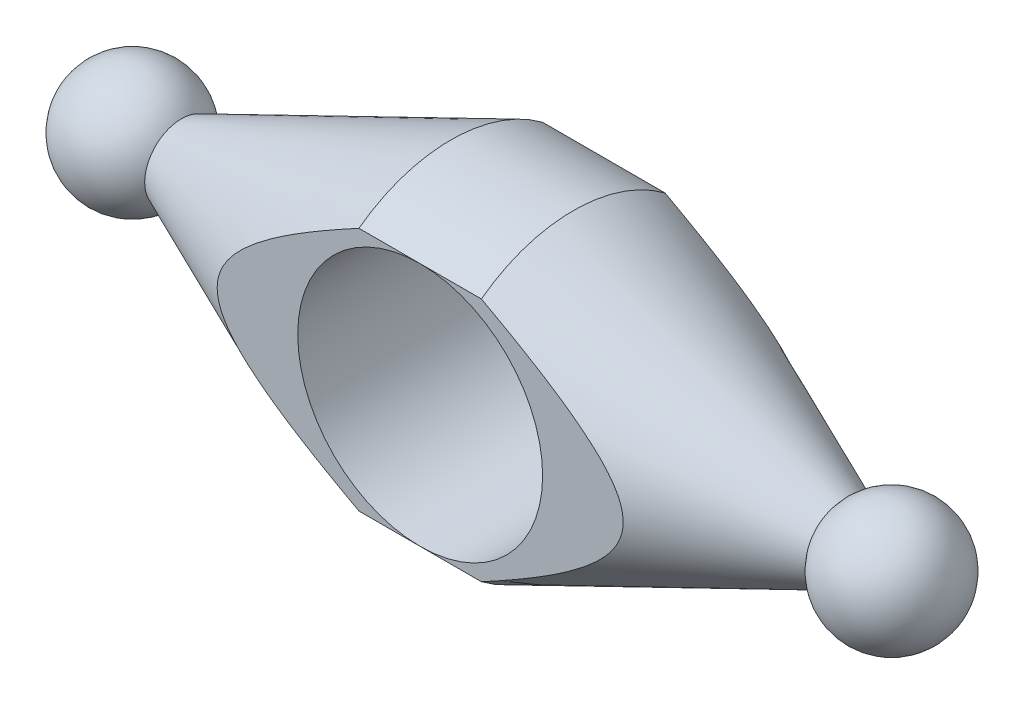
SolidWorks part; units mm, degrees
ref_plane "Спереди" through (0, 0, 0) normal (0, 0, 1) x (1, 0, 0)
ref_plane "Сверху" through (0, 0, 0) normal (0, 1, 0) x (1, 0, 0)
ref_plane "Справа" through (0, 0, 0) normal (1, 0, 0) x (0, 0, -1)
other "Configuration Table"
sketch "Эскиз1" plane through (0, 0, 0) normal (0, 0, 1) x (1, 0, 0)
  line L0 (0, 0) -> (301.8185, 0) construction
  line L1 (9, 3) -> (31, 12.5)
  line L2 (31, 12.5) -> (41, 12.5)
  line L3 (36, 12.5) -> (36, 24.2241) construction
  line L4 (63, 3) -> (41, 12.5)
  line L5 (0, 0) -> (72, 0)
  arc A0 (0, 0) -> (9, 3) centre (5, 0) cw
  arc A1 (72, 0) -> (63, 3) centre (67, 0) ccw
  dimension "D1" = 5
  dimension "D5" = 6
  dimension "D2" = 36
  dimension "D3" = 25
  dimension "D4" = 5
revolve "Повернуть1" add sketch "Эскиз1" angle 360 about L5
sketch "Эскиз2" plane through (0, 0, 0) normal (0, 0, 1) x (1, 0, 0)
  line L0 (0, 0) -> (79.6493, 0) construction
  line L1 (36, 0) -> (36, 26.1641) construction
  dimension "D1" = 36
ref_plane "Плоскость1" through (36, 0, 0) normal (1, 0, 0) x (0, 0, -1)
sketch "Эскиз4" plane through (36, 0, 0) normal (1, 0, 0) x (0, 0, -1)
  line L0 (-7.5, 10) -> (7.5, 10)
  line L1 (0, 0) -> (0, 26.1641) construction
  line L2 (7.5, 10) -> (7.5, 20)
  line L3 (7.5, 20) -> (15, 20)
  line L4 (15, 20) -> (15, 0)
  line L5 (0, 0) -> (29.9402, 0) construction
  line L6 (0, 0) -> (0, 17.1635) construction
  line L7 (-15, 20) -> (-15, 0)
  line L8 (-7.5, 20) -> (-15, 20)
  line L9 (-7.5, 10) -> (-7.5, 20)
  line L10 (15, 0) -> (-15, 0)
  point P15 (0, 10)
  dimension "D1" = 20
  dimension "D2" = 7.5
  dimension "D3" = 40
  dimension "D4" = 15
revolve "Вырез-Повернуть1" cut sketch "Эскиз4" angle 360 about L5
